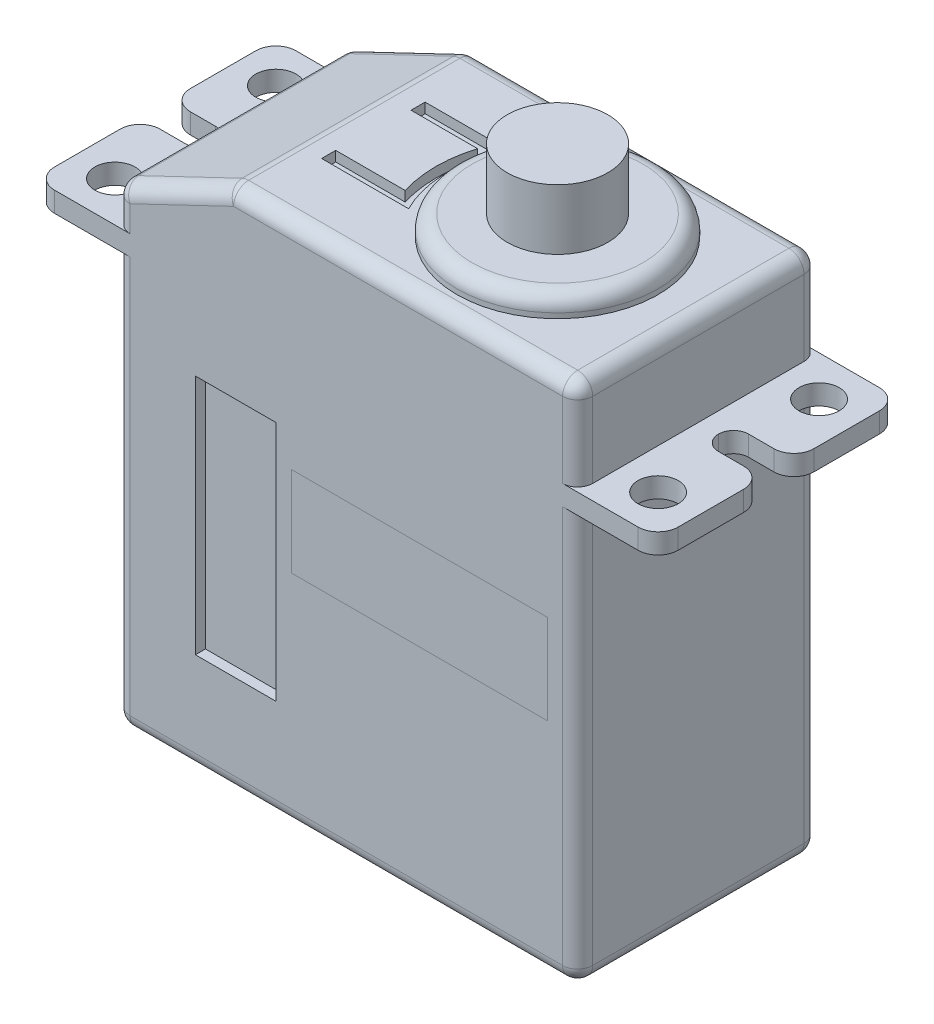
SolidWorks part; units mm, degrees
ref_plane "Front Plane" through (0, 0, 0) normal (0, 0, 1) x (1, 0, 0)
ref_plane "Top Plane" through (0, 0, 0) normal (0, 1, 0) x (1, 0, 0)
ref_plane "Right Plane" through (0, 0, 0) normal (1, 0, 0) x (0, 0, -1)
sketch "Sketch1" plane through (0, 0, 0) normal (0, 0, 1) x (1, 0, 0)
  line L1 (0, 0) -> (23, 0)
  line L2 (0, 0) -> (0, 26)
  line L3 (0, 26) -> (23, 26)
  line L4 (23, 0) -> (23, 26)
  dimension "D1" = 26
  dimension "D2" = 23
extrude "Boss-Extrude1" add sketch "Sketch1" along normal blind 12
sketch "Sketch2" plane through (0, 0, 12) normal (0, 0, 1) x (1, 0, 0)
  line L0 (5.726, 26) -> (0, 23.2609)
  line L1 (23, 26) -> (0, 26) construction
  line L2 (0, 26) -> (0, 0) construction
  line L3 (0, 23.2609) -> (0, 26)
  line L4 (0, 26) -> (5.726, 26)
extrude "Cut-Extrude1" cut sketch "Sketch2" against normal blind 12
sketch "Sketch3" plane through (0, 0, 0) normal (-1, 0, 0) x (0, 0, 1)
  line L0 (0, 23.2609) -> (0, 0) construction
  line L1 (0, 21.5) -> (12, 21.5)
  line L2 (0, 21.5) -> (0, 20.5)
  line L3 (0, 20.5) -> (12, 20.5)
  line L4 (12, 21.5) -> (12, 20.5)
  line L5 (12, 23.2609) -> (12, 0) construction
  line L6 (12, 0) -> (0, 0) construction
  dimension "D1" = 1
  dimension "D2" = 20.5
extrude "Boss-Extrude2" add sketch "Sketch3" along normal blind 4 and the other way blind 27
sketch "Sketch5" plane through (0, 21.5, 0) normal (0, 1, 0) x (1, 0, 0)
  line L0 (0, 0) -> (-4, 0) construction
  line L1 (27, 0) -> (23, 0) construction
  line L2 (0, -12) -> (-4, -12) construction
  line L3 (27, -12) -> (23, -12) construction
  circle A0 centre (-2, -10) radius 1
  circle A1 centre (-2, -2) radius 1
  circle A2 centre (25, -2) radius 1
  circle A3 centre (25, -10) radius 1
  point P10 (-2, 0)
  point P13 (25, 0)
  dimension "D5" = 2
  dimension "D1" = 2
  dimension "D2" = 2
  dimension "D3" = 2
  dimension "D4" = 2
extrude "Cut-Extrude2" cut sketch "Sketch5" against normal blind 5
sketch "Sketch6" plane through (0, 21.5, 0) normal (0, 1, 0) x (1, 0, 0)
  line L0 (-4, -12) -> (-4, 0) construction
  line L1 (-4, -5.25) -> (-1, -5.25)
  line L2 (-4, -5.25) -> (-4, -6.75)
  line L3 (-4, -6.75) -> (-1, -6.75)
  line L4 (-1, -5.25) -> (-1, -6.75)
  line L5 (27, -12) -> (27, 0) construction
  line L6 (27, -5.25) -> (24, -5.25)
  line L7 (27, -5.25) -> (27, -6.75)
  line L8 (27, -6.75) -> (24, -6.75)
  line L9 (24, -5.25) -> (24, -6.75)
  point P12 (-4, -6)
  point P13 (-1, -6)
  point P14 (27, -6)
  point P15 (24, -6)
  dimension "D1" = 1.5
  dimension "D2" = 1.5
  dimension "D3" = 3
  dimension "D4" = 3
extrude "Cut-Extrude3" cut sketch "Sketch6" against normal blind 5
fillet "Fillet1" radius 1 8 edges at (-4, 21, 5.25) (27, 21, 0) (27, 21, 5.25) (27, 21, 6.75) (27, 21, 12) (-4, 21, 12) (-4, 21, 6.75) (-4, 21, 0)
fillet "Fillet2" radius 0.75 4 edges at (-1, 21, 6.75) (-1, 21, 5.25) (24, 21, 6.75) (24, 21, 5.25)
sketch "Sketch7" plane through (0, 26, 0) normal (0, 1, 0) x (1, 0, 0)
  line L0 (23, -12) -> (23, 0) construction
  line L1 (23, -12) -> (23, 0) construction
  circle A0 centre (16, -6) radius 5
  point P4 (23, -6)
  dimension "D1" = 10
  dimension "D2" = 7
extrude "Boss-Extrude3" add sketch "Sketch7" along normal blind 1
sketch "Sketch8" plane through (0, 26, 0) normal (0, 1, 0) x (1, 0, 0)
  line L0 (11.1019, -3.5) -> (6.9174, -3.5)
  line L1 (6.9174, -3.5) -> (6.9174, -4.2)
  line L2 (6.9174, -4.2) -> (10.2291, -4.2)
  line L3 (6.7735, -8.5) -> (11.1019, -8.5)
  line L4 (6.7735, -8.5) -> (6.7735, -7.8)
  line L5 (6.7735, -7.8) -> (10.2291, -7.8)
  line L6 (23, 0) -> (5.726, 0) construction
  line L7 (23, -12) -> (5.726, -12) construction
  arc A0 (11.1019, -3.5) -> (11.1019, -8.5) centre (16, -6) ccw
  arc A1 (10.2291, -4.2) -> (10.2291, -7.8) centre (16, -6) ccw
  dimension "D1" = 0.7
  dimension "D2" = 0.7
  dimension "D3" = 3.5
  dimension "D4" = 3.5
extrude "Cut-Extrude4" cut sketch "Sketch8" against normal blind 0.5
fillet "Fillet3" radius 0.75 20 edges at (23, 0, 6) (11.5, 0, 12) (0, 0, 6) (0, 22.3805, 0) (0, 22.3805, 12) (0, 10.25, 12) (0, 10.25, 0) (11.5, 0, 0) (23, 26, 6) (23, 23.75, 12) (23, 10.25, 12) (23, 10.25, 0) (23, 23.75, 0) (16, 27, 11) (14.363, 26, 12) (2.863, 24.6305, 12) (0, 23.2609, 6) (2.863, 24.6305, 0) (5.726, 26, 6) (14.363, 26, 0)
sketch "Sketch9" plane through (0, 0, 12) normal (0, 0, 1) x (1, 0, 0)
  line L0 (22.25, 0) -> (0.75, 0) construction
  line L1 (4, 17) -> (8, 17)
  line L2 (4, 17) -> (4, 5)
  line L3 (4, 5) -> (8, 5)
  line L4 (8, 17) -> (8, 5)
  line L5 (0, 0.75) -> (0, 20.5) construction
  dimension "D1" = 12
  dimension "D2" = 4
  dimension "D3" = 5
  dimension "D4" = 4
extrude "Cut-Extrude5" cut sketch "Sketch9" against normal blind 0.5
sketch "Sketch10" plane through (0, 27, 0) normal (0, 1, 0) x (1, 0, 0)
  circle A0 centre (16, -6) radius 2.5
  dimension "D1" = 5
extrude "Boss-Extrude4" add sketch "Sketch10" along normal blind 3
sketch "Sketch11" plane through (0, 0, 12) normal (0, 0, 1) x (1, 0, 0)
  line L1 (8.7709, 15.3612) -> (21.4934, 15.3612)
  line L2 (8.7709, 15.3612) -> (8.7709, 10.9063)
  line L3 (8.7709, 10.9063) -> (21.4934, 10.9063)
  line L4 (21.4934, 15.3612) -> (21.4934, 10.9063)
split line "Split Line1"
sketch "Sketch12" plane through (0, 0, 0) normal (0, -1, 0) x (1, 0, 0)
  line L0 (0, 11.25) -> (0, 0.75) construction
  line L1 (23, 0.75) -> (23, 11.25) construction
  line L2 (0.75, 12) -> (22.25, 12) construction
  line L3 (5.8962, 0) -> (22.25, 0) construction
  circle A0 centre (-2, 10) radius 1 construction
  circle A1 centre (25, 10) radius 1 construction
sketch "Sketch13" plane through (0, 26, 0) normal (0, 1, 0) x (1, 0, 0)
  line L0 (5.8962, 0) -> (22.25, 0) construction
  line L1 (22.25, -12) -> (5.8962, -12) construction
  line L2 (-4, -4.25) -> (-4, -1) construction
  line L3 (27, -4.25) -> (27, -1) construction
sketch "Sketch14" plane through (0, 26, 0) normal (0, 1, 0) x (1, 0, 0)
  line L0 (0, -0.75) -> (0, -11.25) construction
  line L1 (23, -11.25) -> (23, -0.75) construction
  line L2 (5.8962, 0) -> (22.25, 0) construction
  line L3 (22.25, -12) -> (5.8962, -12) construction
